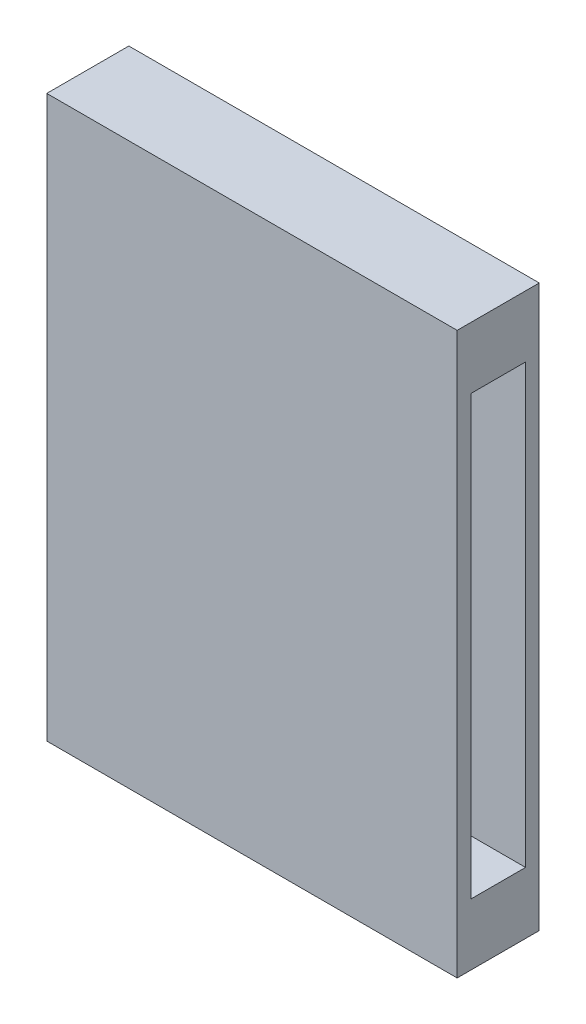
SolidWorks part; units mm, degrees
ref_plane "Top Plane" through (0, 0, 0) normal (0, 0, 1) x (1, 0, 0)
ref_plane "Front Plane" through (0, 0, 0) normal (0, 1, 0) x (1, 0, 0)
ref_plane "Right Plane" through (0, 0, 0) normal (1, 0, 0) x (0, 0, -1)
sketch "Sketch1" plane through (0, 0, 0) normal (0, 0, 1) x (1, 0, 0)
  line L1 (0, 0) -> (30, 0)
  line L2 (0, 0) -> (0, 41)
  line L3 (0, 41) -> (30, 41)
  line L4 (30, 0) -> (30, 41)
  dimension "D1" = 41
  dimension "D2" = 30
extrude "Boss-Extrude1" add sketch "Sketch1" along normal blind 6
sketch "Sketch2" plane through (0, 0, 0) normal (-1, 0, 0) x (0, 0, 1)
  line L14 (1, 40) -> (1, 1)
  line L15 (1, 1) -> (5, 1)
  line L16 (5, 1) -> (5, 40)
  line L17 (5, 40) -> (1, 40)
  line L18 (1, 40) -> (1, 1)
  line L19 (1, 1) -> (5, 1)
  line L20 (5, 1) -> (5, 40)
  line L21 (5, 40) -> (1, 40)
  dimension "D1" = 1
extrude "Cut-Extrude1" cut sketch "Sketch2" against normal blind 21
sketch "Sketch3" plane through (30, 0, 0) normal (1, 0, 0) x (0, 0, -1)
  line L0 (-6, 0) -> (-6, 41) construction
  line L1 (-5, 36.5) -> (-1, 36.5)
  line L2 (-5, 36.5) -> (-5, 4.5)
  line L3 (-5, 4.5) -> (-1, 4.5)
  line L4 (-1, 36.5) -> (-1, 4.5)
  line L5 (-6, 41) -> (0, 41) construction
  dimension "D1" = 32
  dimension "D2" = 4
  dimension "D3" = 1
  dimension "D4" = 4.5
extrude "Cut-Extrude2" cut sketch "Sketch3" against normal blind 21
